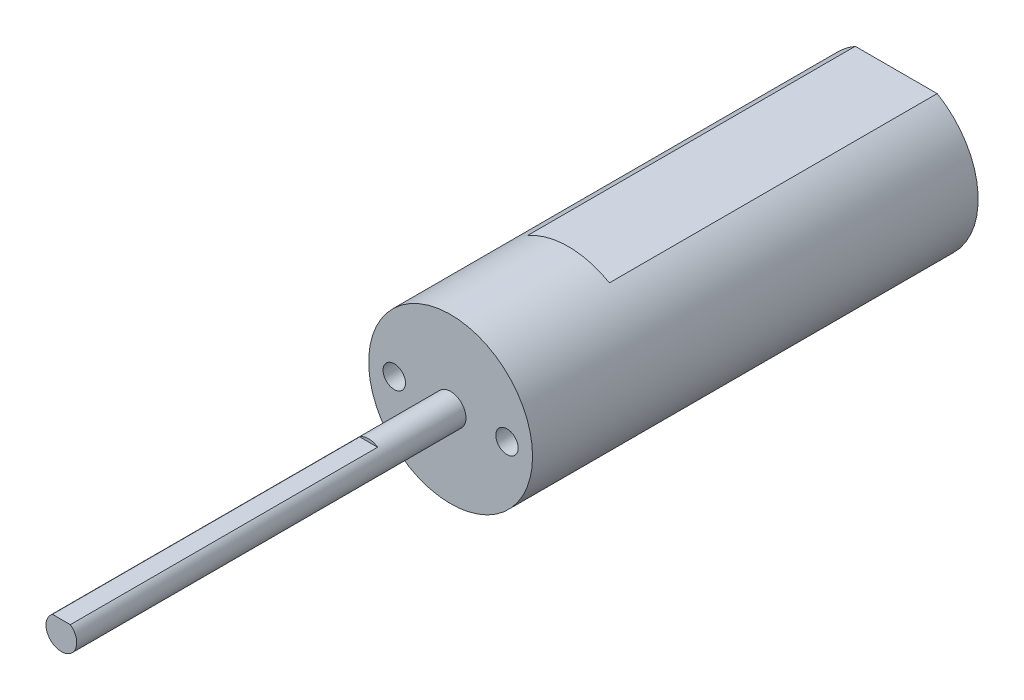
SolidWorks part; units mm, degrees
ref_plane "Front Plane" through (0, 0, 0) normal (0, 0, 1) x (1, 0, 0)
ref_plane "Top Plane" through (0, 0, 0) normal (0, 1, 0) x (1, 0, 0)
ref_plane "Right Plane" through (0, 0, 0) normal (1, 0, 0) x (0, 0, -1)
sketch "Sketch1" plane through (0, 0, 0) normal (0, 0, 1) x (1, 0, 0)
  circle A0 centre (0, 0) radius 8
  dimension "D1" = 16
extrude "Boss-Extrude1" add sketch "Sketch1" along normal blind 32
sketch "Sketch3" plane through (0, 0, 0) normal (0, 0, -1) x (-1, 0, 0)
  line L0 (-4, 6.9282) -> (4, 6.9282)
  line L2 (4, -6.9282) -> (-4, -6.9282)
  circle A0 centre (0, 0) radius 8 construction
  circle A1 centre (0, 0) radius 8
  point P4 (0, 0)
  point P7 (4.3194, 9.019)
  circle M2 centre (0, 0) radius 8
  dimension "D1" = 8
extrude "Cut-Extrude1" cut sketch "Sketch3" against normal blind 32 contours L0 M2 | L2 M2 region at (0, 7.3595, 0) region at (0, -7.3595, 0)
sketch "Sketch4" plane through (0, 0, 32) normal (0, 0, 1) x (1, 0, 0)
  circle A0 centre (0, 0) radius 8
  arc A1 (4, -6.9282) -> (4, 6.9282) centre (0, 0) ccw construction
extrude "Boss-Extrude2" add sketch "Sketch4" along normal blind 11.5
sketch "Sketch5" plane through (0, 0, 43.5) normal (0, 0, 1) x (1, 0, 0)
  line L0 (-5.5, 0) -> (0, 0) construction
  line L1 (0, 0) -> (5.5, 0) construction
  circle A0 centre (0, 0) radius 1.5
  circle A1 centre (-5.5, 0) radius 1.0922
  circle A2 centre (5.5, 0) radius 1.0922
  dimension "D2" = 2.1844
  dimension "D3" = 3
  dimension "D1" = 11
extrude "Cut-Extrude2" cut sketch "Sketch5" against normal blind 6 contours A2 | A1
extrude "Boss-Extrude3" add sketch "Sketch5<3>" along normal blind 38 contours A0 region at (0, 0, 43.5)
sketch "Sketch5<3>" plane through (0, 0, 43.5) normal (0, 0, 1) x (1, 0, 0) same geometry as "Sketch5"
sketch "Sketch6" plane through (0, 0, 81.5) normal (0, 0, 1) x (1, 0, 0)
  line L0 (0.875, 1.2183) -> (-0.875, 1.2183)
  circle A0 centre (0, 0) radius 1.5 construction
  circle A2 centre (0, 0) radius 1.5
  circle A3 centre (0, 0) radius 1.5
  circle M3 centre (0, 0) radius 1.5
  dimension "D2" = 1.75
  dimension "D1" = 0
extrude "Cut-Extrude3" cut sketch "Sketch6" against normal blind 30 contours L0 M3 region at (0, 1.332, 81.5)
